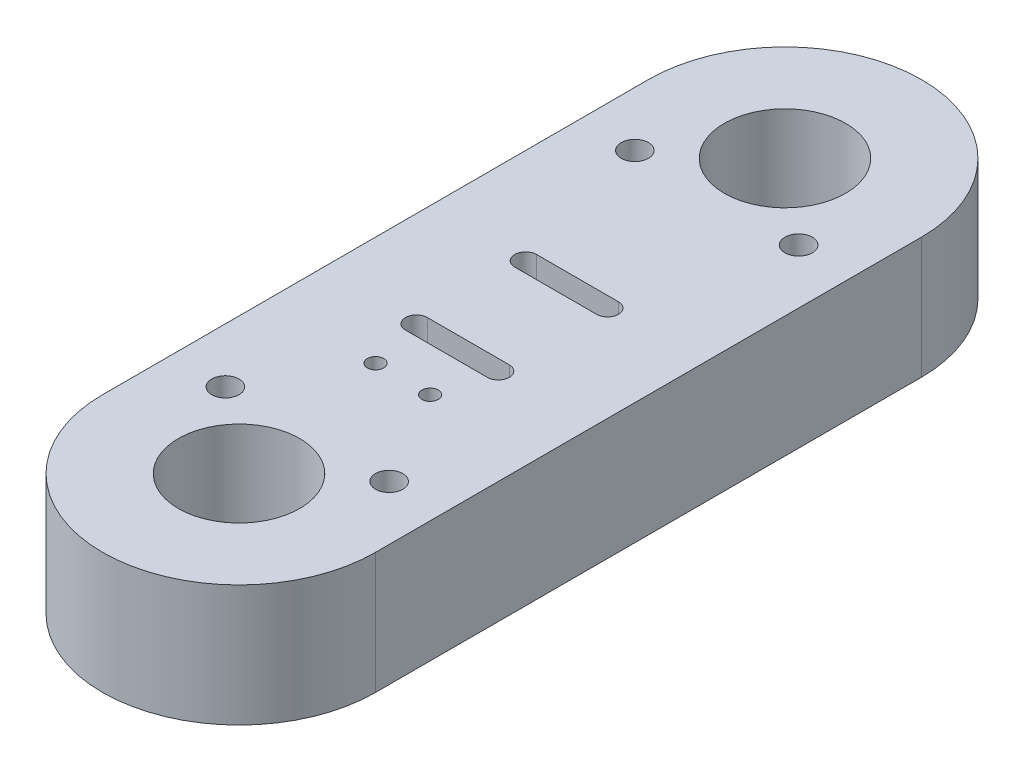
SolidWorks part; units mm, degrees
material "Nylon 101"
ref_plane "Front" through (0, 0, 0) normal (0, 0, 1) x (1, 0, 0)
ref_plane "Top" through (0, 0, 0) normal (0, 1, 0) x (1, 0, 0)
ref_plane "Right" through (0, 0, 0) normal (1, 0, 0) x (0, 0, -1)
sketch "Sketch1" plane through (0, 0, 0) normal (0, 1, 0) x (1, 0, 0)
  line L0 (-7.5, 10) -> (7.5, 10) construction
  line L1 (-15, 37.5) -> (15, 37.5) construction
  line L2 (0, -50) -> (0, 50) construction
  line L3 (-25, -50) -> (-25, 50)
  line L4 (25, -50) -> (25, 50)
  line L10 (-15, 37.5) -> (-15, -37.5) construction
  line L11 (-15, -37.5) -> (15, -37.5) construction
  line L12 (15, 37.5) -> (15, -37.5) construction
  line L13 (-7.5, 12) -> (7.5, 12)
  line L14 (0, 0) -> (15, 0) construction
  line L15 (-7.5, 8) -> (7.5, 8)
  line L16 (-7.5, -10) -> (7.5, -10) construction
  line L17 (-7.5, -12) -> (7.5, -12)
  line L18 (-7.5, -8) -> (7.5, -8)
  line L19 (-5, -20) -> (5, -20) construction
  circle A0 centre (0, 50) radius 6.35 construction
  circle A1 centre (0, -50) radius 6.35 construction
  arc A2 (-25, -50) -> (25, -50) centre (0, -50) ccw
  arc A3 (25, 50) -> (-25, 50) centre (0, 50) ccw
  circle A6 centre (-15, 37.5) radius 2.5
  circle A7 centre (-15, -37.5) radius 2.5
  circle A8 centre (15, -37.5) radius 2.5
  circle A9 centre (15, 37.5) radius 2.5
  circle A10 centre (0, -50) radius 11.1125
  circle A11 centre (0, 50) radius 11.1125
  arc A12 (-7.5, 12) -> (-7.5, 8) centre (-7.5, 10) ccw
  arc A13 (7.5, 8) -> (7.5, 12) centre (7.5, 10) ccw
  arc A14 (-7.5, -12) -> (-7.5, -8) centre (-7.5, -10) cw
  arc A15 (7.5, -8) -> (7.5, -12) centre (7.5, -10) cw
  circle A16 centre (-5, -20) radius 1.5
  circle A17 centre (5, -20) radius 1.5
  point P8 (0, 0)
  point P24 (0, -37.5)
  point P25 (0, 10)
  point P35 (0, -20)
  point P38 (0, -10)
  dimension "D2" = 12.7
  dimension "D5" = 25
  dimension "D1" = 5
  dimension "D7" = 22.225
  dimension "D8" = 10
  dimension "D11" = 2
  dimension "D13" = 3
  dimension "D3" = 100
  dimension "D4" = 12.5
  dimension "D6" = 12.5
  dimension "D9" = 30
  dimension "D10" = 15
  dimension "D12" = 10
  dimension "D14" = 10
extrude "Boss-Extrude1" add sketch "Sketch1" along normal blind 22.23 contours A1 L4 A0 L3 A9 A8 A7 A6 region at (0, 0, -0.0475)
